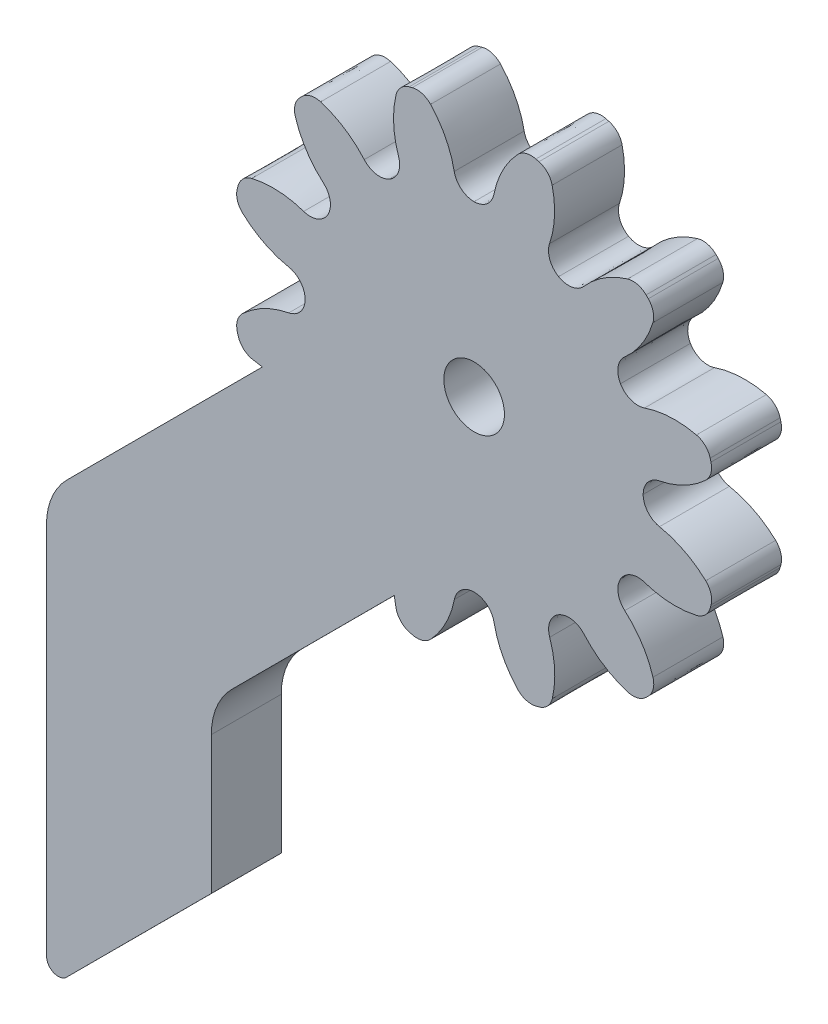
SolidWorks part; units mm, degrees
ref_plane "Front Plane" through (0, 0, 0) normal (0, 0, 1) x (1, 0, 0)
ref_plane "Top Plane" through (0, 0, 0) normal (0, 1, 0) x (1, 0, 0)
ref_plane "Right Plane" through (0, 0, 0) normal (1, 0, 0) x (0, 0, -1)
sketch "Model" plane through (0, 0, 0) normal (0, 0, 1) x (1, 0, 0)
  line L0 (37.1951, 19.5355) -> (37.1896, 26.0412)
  line L1 (44.264, 25.402) -> (38.0477, 19.1811)
  line L2 (46.4502, 46.0515) -> (38.0674, 37.6629)
  line L3 (45.14, 33.4228) -> (52.109, 40.3967)
  line L4 (44.2621, 31.3011) -> (44.264, 25.402)
  line L5 (37.1895, 35.5412) -> (37.1896, 26.0412)
  circle A0 centre (55.534, 49.4829) radius 1.3
  arc A2 (38.0674, 37.6629) -> (37.1895, 35.5412) centre (40.1895, 35.5424) ccw
  arc A3 (45.14, 33.4228) -> (44.2621, 31.3011) centre (47.2616, 31.3024) ccw
  arc A4 (37.1951, 19.5355) -> (38.0488, 19.1822) centre (37.6951, 19.5357) ccw
  spline S0 degree 3 poles (54.6867, 41.5337) (54.5406, 40.7904) (54.1887, 40.1031) (53.6712, 39.5501) knots 0 0 0 0 1 1 1 1
  spline S1 degree 3 poles (58.7749, 42.175) (59.0199, 41.4583) (59.0588, 40.6872) (58.8872, 39.9494) knots 0 0 0 0 1 1 1 1
  spline S2 degree 3 poles (61.9946, 44.7745) (62.5652, 44.2763) (62.9845, 43.628) (63.2047, 42.9032) knots 0 0 0 0 1 1 1 1
  spline S3 degree 3 poles (63.4833, 48.6356) (64.2264, 48.4895) (64.9137, 48.1376) (65.4669, 47.6201) knots 0 0 0 0 1 1 1 1
  spline S4 degree 3 poles (62.8419, 52.7238) (63.5586, 52.9689) (64.3298, 53.0077) (65.0675, 52.836) knots 0 0 0 0 1 1 1 1
  spline S5 degree 3 poles (60.2424, 55.9435) (60.7405, 56.5141) (61.3889, 56.9334) (62.1137, 57.1537) knots 0 0 0 0 1 1 1 1
  spline S6 degree 3 poles (56.3813, 57.4322) (56.5275, 58.1754) (56.8792, 58.8626) (57.3968, 59.4158) knots 0 0 0 0 1 1 1 1
  spline S7 degree 3 poles (52.2932, 56.7909) (52.0481, 57.5075) (52.0092, 58.2786) (52.1808, 59.0164) knots 0 0 0 0 1 1 1 1
  spline S8 degree 3 poles (49.0734, 54.1913) (48.5028, 54.6895) (48.0835, 55.3379) (47.8633, 56.0626) knots 0 0 0 0 1 1 1 1
  spline S9 degree 3 poles (47.5847, 50.3302) (46.8415, 50.4763) (46.1542, 50.8281) (45.6011, 51.3457) knots 0 0 0 0 1 1 1 1
  spline S10 degree 3 poles (46.4502, 46.0515) (46.2989, 46.0691) (46.1488, 46.0952) (46.0004, 46.1297) knots 0 0 0 0 1 1 1 1
  spline S11 degree 3 poles (54.6867, 41.5337) (54.7665, 41.9398) (55.1226, 42.2327) (55.5365, 42.2329) knots 0 0 0 0 0.333333 0.333333 0.333333 0.333333
  spline S12 degree 3 poles (55.5365, 42.2329) (55.9505, 42.233) (56.3067, 41.9403) (56.3869, 41.5342) knots 0.333333 0.333333 0.333333 0.333333 1 1 1 1
  spline S13 degree 3 poles (52.8852, 39.3225) (52.8417, 39.3338) (52.7982, 39.3455) (52.7548, 39.3574) knots 0 0 0 0 1 1 1 1
  spline S14 degree 3 poles (53.6712, 39.5501) (53.4708, 39.3358) (53.1691, 39.2484) (52.8852, 39.3225) knots 0 0 0 0 1 1 1 1
  spline S15 degree 3 poles (52.1874, 39.947) (52.1529, 40.0953) (52.1267, 40.2454) (52.109, 40.3967) knots 0 0 0 0 1 1 1 1
  spline S16 degree 3 poles (52.7548, 39.3574) (52.4719, 39.435) (52.2542, 39.6614) (52.1874, 39.947) knots 0 0 0 0 1 1 1 1
  spline S17 degree 3 poles (58.7749, 42.175) (58.6409, 42.5667) (58.8028, 42.9984) (59.1612, 43.2055) knots 0 0 0 0 0.333333 0.333333 0.333333 0.333333
  spline S18 degree 3 poles (59.1612, 43.2055) (59.5197, 43.4126) (59.9745, 43.3372) (60.247, 43.0256) knots 0.333333 0.333333 0.333333 0.333333 1 1 1 1
  spline S19 degree 3 poles (58.3203, 39.3593) (58.2769, 39.3474) (58.2334, 39.3357) (58.1899, 39.3244) knots 0 0 0 0 1 1 1 1
  spline S20 degree 3 poles (58.8872, 39.9494) (58.8207, 39.6636) (58.6032, 39.4372) (58.3203, 39.3593) knots 0 0 0 0 1 1 1 1
  spline S21 degree 3 poles (57.4037, 39.5513) (56.8858, 40.1041) (56.5335, 40.7911) (56.3869, 41.5342) knots 0 0 0 0 1 1 1 1
  spline S22 degree 3 poles (58.1899, 39.3244) (57.9061, 39.2501) (57.6043, 39.3372) (57.4037, 39.5513) knots 0 0 0 0 1 1 1 1
  spline S23 degree 3 poles (61.9946, 44.7745) (61.6828, 45.0467) (61.6071, 45.5015) (61.814, 45.8602) knots 0 0 0 0 0.333333 0.333333 0.333333 0.333333
  spline S24 degree 3 poles (61.814, 45.8602) (62.0208, 46.2187) (62.4524, 46.3809) (62.8442, 46.2472) knots 0.333333 0.333333 0.333333 0.333333 1 1 1 1
  spline S25 degree 3 poles (63.0088, 42.1088) (62.9772, 42.0767) (62.9454, 42.0449) (62.9134, 42.0133) knots 0 0 0 0 1 1 1 1
  spline S26 degree 3 poles (63.2047, 42.9032) (63.29, 42.6225) (63.2149, 42.3177) (63.0088, 42.1088) knots 0 0 0 0 1 1 1 1
  spline S27 degree 3 poles (62.1191, 41.8168) (61.3942, 42.0365) (60.7456, 42.4554) (60.247, 43.0256) knots 0 0 0 0 1 1 1 1
  spline S28 degree 3 poles (62.9134, 42.0133) (62.7047, 41.807) (62.3998, 41.7317) (62.1191, 41.8168) knots 0 0 0 0 1 1 1 1
  spline S29 degree 3 poles (63.4833, 48.6356) (63.0771, 48.7155) (62.7841, 49.0715) (62.7841, 49.4855) knots 0 0 0 0 0.333333 0.333333 0.333333 0.333333
  spline S30 degree 3 poles (62.7841, 49.4855) (62.7839, 49.8995) (63.0765, 50.2556) (63.4827, 50.3358) knots 0.333333 0.333333 0.333333 0.333333 1 1 1 1
  spline S31 degree 3 poles (65.6944, 46.8341) (65.683, 46.7906) (65.6714, 46.7471) (65.6595, 46.7037) knots 0 0 0 0 1 1 1 1
  spline S32 degree 3 poles (65.4669, 47.6201) (65.6811, 47.4196) (65.7684, 47.118) (65.6944, 46.8341) knots 0 0 0 0 1 1 1 1
  spline S33 degree 3 poles (65.0698, 46.1363) (64.3322, 45.9643) (63.5611, 46.0026) (62.8442, 46.2472) knots 0 0 0 0 1 1 1 1
  spline S34 degree 3 poles (65.6595, 46.7037) (65.5818, 46.4208) (65.3556, 46.203) (65.0698, 46.1363) knots 0 0 0 0 1 1 1 1
  spline S35 degree 3 poles (62.8419, 52.7238) (62.4502, 52.5899) (62.0185, 52.7517) (61.8115, 53.1101) knots 0 0 0 0 0.333333 0.333333 0.333333 0.333333
  spline S36 degree 3 poles (61.8115, 53.1101) (61.6043, 53.4685) (61.6797, 53.9233) (61.9913, 54.1958) knots 0.333333 0.333333 0.333333 0.333333 1 1 1 1
  spline S37 degree 3 poles (65.6575, 52.2692) (65.6695, 52.2258) (65.6812, 52.1823) (65.6926, 52.1388) knots 0 0 0 0 1 1 1 1
  spline S38 degree 3 poles (65.0675, 52.836) (65.3532, 52.7696) (65.5797, 52.5521) (65.6575, 52.2692) knots 0 0 0 0 1 1 1 1
  spline S39 degree 3 poles (65.4655, 51.3526) (64.9128, 50.8347) (64.2258, 50.4824) (63.4827, 50.3358) knots 0 0 0 0 1 1 1 1
  spline S40 degree 3 poles (65.6926, 52.1388) (65.7668, 51.855) (65.6796, 51.5532) (65.4655, 51.3526) knots 0 0 0 0 1 1 1 1
  spline S41 degree 3 poles (60.2424, 55.9435) (59.9701, 55.6317) (59.5153, 55.556) (59.1568, 55.7629) knots 0 0 0 0 0.333333 0.333333 0.333333 0.333333
  spline S42 degree 3 poles (59.1568, 55.7629) (58.7982, 55.9697) (58.636, 56.4013) (58.7697, 56.7931) knots 0.333333 0.333333 0.333333 0.333333 1 1 1 1
  spline S43 degree 3 poles (62.9081, 56.9577) (62.9401, 56.926) (62.972, 56.8943) (63.0037, 56.8622) knots 0 0 0 0 1 1 1 1
  spline S44 degree 3 poles (62.1137, 57.1537) (62.3944, 57.239) (62.6992, 57.1637) (62.9081, 56.9577) knots 0 0 0 0 1 1 1 1
  spline S45 degree 3 poles (63.2001, 56.0679) (62.9804, 55.3431) (62.5616, 54.6944) (61.9913, 54.1958) knots 0 0 0 0 1 1 1 1
  spline S46 degree 3 poles (63.0037, 56.8622) (63.2098, 56.6535) (63.2852, 56.3487) (63.2001, 56.0679) knots 0 0 0 0 1 1 1 1
  spline S47 degree 3 poles (56.3813, 57.4322) (56.3014, 57.026) (55.9454, 56.733) (55.5314, 56.7329) knots 0 0 0 0 0.333333 0.333333 0.333333 0.333333
  spline S48 degree 3 poles (55.5314, 56.7329) (55.1175, 56.7327) (54.7612, 57.0254) (54.6811, 57.4316) knots 0.333333 0.333333 0.333333 0.333333 1 1 1 1
  spline S49 degree 3 poles (58.1828, 59.6433) (58.2263, 59.632) (58.2698, 59.6203) (58.3132, 59.6085) knots 0 0 0 0 1 1 1 1
  spline S50 degree 3 poles (57.3968, 59.4158) (57.5972, 59.63) (57.8989, 59.7173) (58.1828, 59.6433) knots 0 0 0 0 1 1 1 1
  spline S51 degree 3 poles (58.8805, 59.0187) (59.0527, 58.2812) (59.0143, 57.51) (58.7697, 56.7931) knots 0 0 0 0 1 1 1 1
  spline S52 degree 3 poles (58.3132, 59.6085) (58.5961, 59.5307) (58.8139, 59.3045) (58.8805, 59.0187) knots 0 0 0 0 1 1 1 1
  spline S53 degree 3 poles (52.2932, 56.7909) (52.427, 56.3991) (52.2652, 55.9674) (51.9068, 55.7603) knots 0 0 0 0 0.333333 0.333333 0.333333 0.333333
  spline S54 degree 3 poles (51.9068, 55.7603) (51.5484, 55.5532) (51.0935, 55.6285) (50.8211, 55.9403) knots 0.333333 0.333333 0.333333 0.333333 1 1 1 1
  spline S55 degree 3 poles (52.7477, 59.6065) (52.7911, 59.6184) (52.8345, 59.6301) (52.8781, 59.6414) knots 0 0 0 0 1 1 1 1
  spline S56 degree 3 poles (52.1808, 59.0164) (52.2473, 59.3021) (52.4648, 59.5286) (52.7477, 59.6065) knots 0 0 0 0 1 1 1 1
  spline S57 degree 3 poles (53.6642, 59.4144) (54.1821, 58.8617) (54.5344, 58.1747) (54.6811, 57.4316) knots 0 0 0 0 1 1 1 1
  spline S58 degree 3 poles (52.8781, 59.6414) (53.1619, 59.7157) (53.4636, 59.6285) (53.6642, 59.4144) knots 0 0 0 0 1 1 1 1
  spline S59 degree 3 poles (49.0734, 54.1913) (49.3853, 53.9191) (49.4609, 53.4642) (49.254, 53.1058) knots 0 0 0 0 0.333333 0.333333 0.333333 0.333333
  spline S60 degree 3 poles (49.254, 53.1058) (49.0472, 52.7471) (48.6156, 52.585) (48.2238, 52.7186) knots 0.333333 0.333333 0.333333 0.333333 1 1 1 1
  spline S61 degree 3 poles (48.0592, 56.857) (48.0908, 56.889) (48.1227, 56.9209) (48.1546, 56.9526) knots 0 0 0 0 1 1 1 1
  spline S62 degree 3 poles (47.8633, 56.0626) (47.778, 56.3434) (47.8532, 56.6482) (48.0592, 56.857) knots 0 0 0 0 1 1 1 1
  spline S63 degree 3 poles (48.949, 57.149) (49.6738, 56.9293) (50.3225, 56.5105) (50.8211, 55.9403) knots 0 0 0 0 1 1 1 1
  spline S64 degree 3 poles (48.1546, 56.9526) (48.3633, 57.1587) (48.6681, 57.2341) (48.949, 57.149) knots 0 0 0 0 1 1 1 1
  spline S65 degree 3 poles (47.5847, 50.3302) (47.9909, 50.2503) (48.2839, 49.8943) (48.284, 49.4804) knots 0 0 0 0 0.333333 0.333333 0.333333 0.333333
  spline S66 degree 3 poles (48.284, 49.4804) (48.2841, 49.0664) (47.9915, 48.7102) (47.5853, 48.6301) knots 0.333333 0.333333 0.333333 0.333333 1 1 1 1
  spline S67 degree 3 poles (45.3736, 52.1316) (45.3849, 52.1752) (45.3966, 52.2187) (45.4085, 52.2621) knots 0 0 0 0 1 1 1 1
  spline S68 degree 3 poles (45.6011, 51.3457) (45.3868, 51.5461) (45.2995, 51.8477) (45.3736, 52.1316) knots 0 0 0 0 1 1 1 1
  spline S69 degree 3 poles (45.9981, 52.8294) (46.7358, 53.0015) (47.5069, 52.9632) (48.2238, 52.7186) knots 0 0 0 0 1 1 1 1
  spline S70 degree 3 poles (45.4085, 52.2621) (45.4861, 52.545) (45.7124, 52.7627) (45.9981, 52.8294) knots 0 0 0 0 1 1 1 1
  spline S71 degree 3 poles (45.4104, 46.6965) (45.3984, 46.74) (45.3869, 46.7835) (45.3754, 46.827) knots 0 0 0 0 1 1 1 1
  spline S72 degree 3 poles (46.0004, 46.1297) (45.7147, 46.1961) (45.4883, 46.4137) (45.4104, 46.6965) knots 0 0 0 0 1 1 1 1
  spline S73 degree 3 poles (45.6024, 47.6131) (46.1552, 48.131) (46.8422, 48.4833) (47.5853, 48.6301) knots 0 0 0 0 1 1 1 1
  spline S74 degree 3 poles (45.3754, 46.827) (45.3013, 47.1109) (45.3883, 47.4125) (45.6024, 47.6131) knots 0 0 0 0 1 1 1 1
extrude "Boss-Extrude1" add sketch "Model" along normal blind 3 contours S74 S71 S72 S10 L2 A2 L5 L0 A4 L1 L4 A3 L3 S15 S16 S13 S14 S0 S11 S12 S21 S22 S19 S20 S1 S17 S18 S27 S28 S25 S26 S2 S23 S24 S33 S34 S31 S32 S3 S29 S30 S39 S40 S37 S38 S4 S35 S36 S45 S46 region at (49.9773, 42.721, 0)
